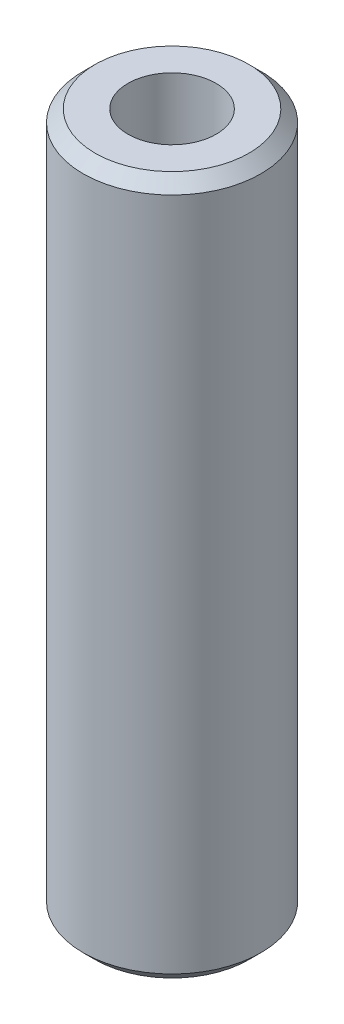
SolidWorks part; units mm, degrees
ref_plane "Front Plane" through (0, 0, 0) normal (0, 0, 1) x (1, 0, 0)
ref_plane "Top Plane" through (0, 0, 0) normal (0, 1, 0) x (1, 0, 0)
ref_plane "Right Plane" through (0, 0, 0) normal (1, 0, 0) x (0, 0, -1)
sketch "Sketch1" plane through (0, 0, 0) normal (0, 1, 0) x (1, 0, 0)
  circle A0 centre (0, 0) radius 10
  dimension "SHAFT_OD" = 20
extrude "Boss-Extrude1" add sketch "Sketch1" along normal blind 78.6237
sketch "Sketch2" plane through (0, 0, 0) normal (0, 1, 0) x (1, 0, 0)
  circle A0 centre (0, 0) radius 4.9652
  dimension "BORE_D" = 9.9305
extrude "Cut-Extrude1" cut sketch "Sketch2" along normal through all
chamfer "Chamfer1" distance 1.3391 angle 45 2 edges at (0, 78.6237, 10) (0, 0, 10)
